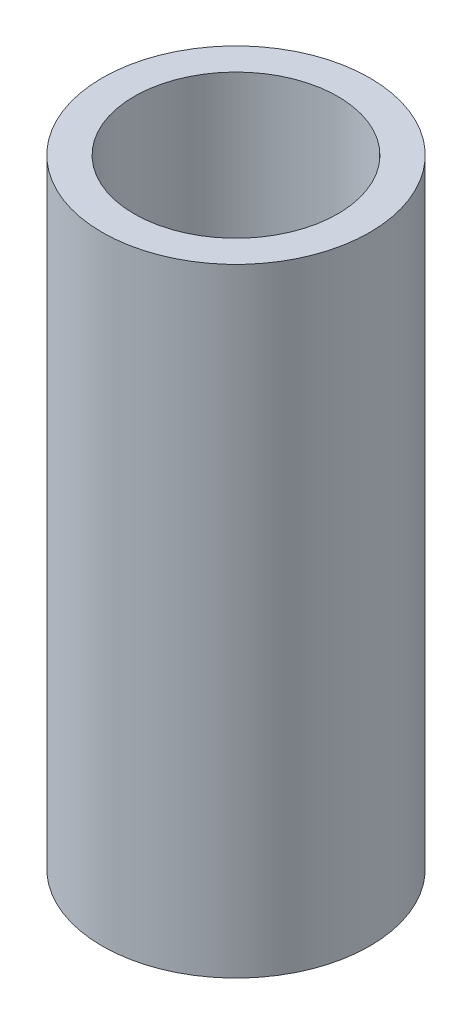
SolidWorks part; units mm, degrees
ref_plane "Front Plane" through (0, 0, 0) normal (0, 0, 1) x (1, 0, 0)
ref_plane "Top Plane" through (0, 0, 0) normal (0, 1, 0) x (1, 0, 0)
ref_plane "Right Plane" through (0, 0, 0) normal (1, 0, 0) x (0, 0, -1)
sketch "Sketch1" plane through (0, 0, 0) normal (0, 1, 0) x (1, 0, 0)
  circle A0 centre (0, 0) radius 12.5
  dimension "SLEEVE_OD" = 25
extrude "Boss-Extrude1" add sketch "Sketch1" along normal blind 57.7376
sketch "Sketch2" plane through (0, 0, 0) normal (0, 1, 0) x (1, 0, 0)
  circle A0 centre (0, 0) radius 9.5096
  dimension "BORE_D" = 19.0191
extrude "Cut-Extrude1" cut sketch "Sketch2" along normal through all
chamfer "Chamfer1" distance 1.7682 angle 45 rebuild error yes
